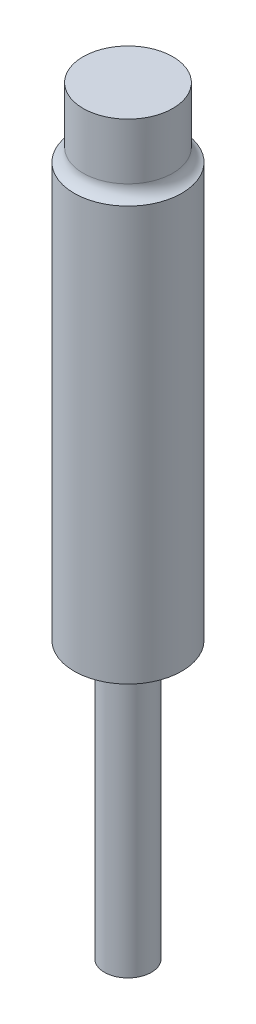
SolidWorks part; units mm, degrees
ref_plane "Alzado" through (0, 0, 0) normal (0, 0, 1) x (1, 0, 0)
ref_plane "Planta" through (0, 0, 0) normal (0, 1, 0) x (1, 0, 0)
ref_plane "Vista lateral" through (0, 0, 0) normal (1, 0, 0) x (0, 0, -1)
sketch "Croquis1" plane through (0, 0, 0) normal (0, 1, 0) x (1, 0, 0)
  circle A0 centre (0, 0) radius 3.9
  dimension "D1" = 7.8
extrude "Saliente-Extruir1" add sketch "Croquis1" along normal blind 30
sketch "Croquis2" plane through (0, 30, 0) normal (0, 1, 0) x (1, 0, 0)
  circle A0 centre (0, 0) radius 3.25
  dimension "D1" = 6.5
extrude "Saliente-Extruir2" add sketch "Croquis2" along normal blind 5
sketch "Croquis3" plane through (0, 0, 0) normal (0, -1, 0) x (1, 0, 0)
  circle A0 centre (0, 0) radius 1.7
  dimension "D1" = 3.4
extrude "Saliente-Extruir3" add sketch "Croquis3" along normal blind 20
fillet "Redondeo1" radius 1 1 edges at (0, 30, 3.25)
